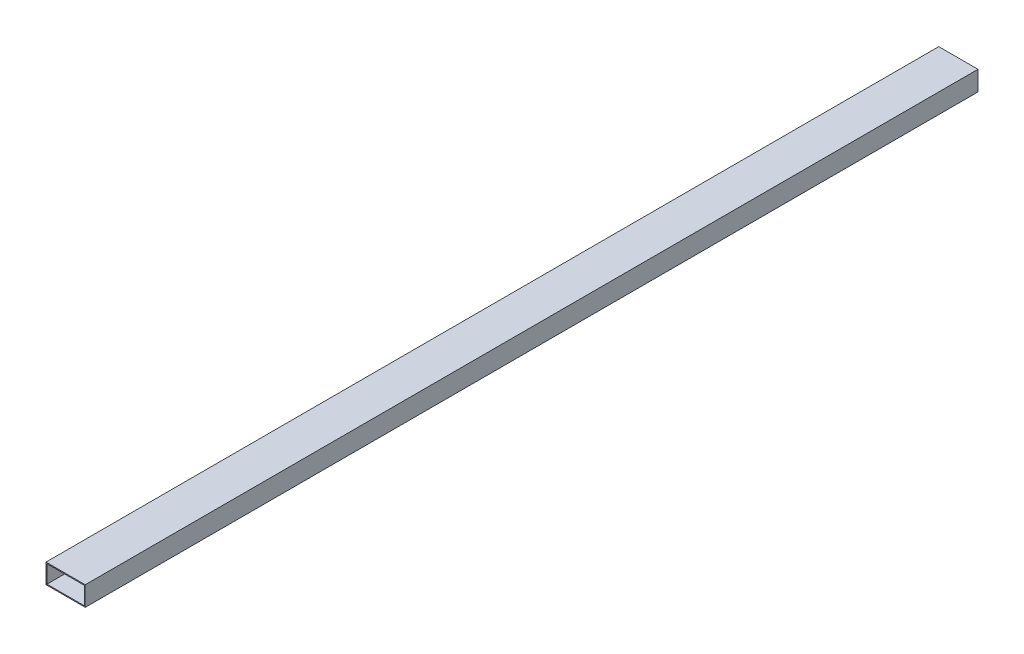
SolidWorks part; units mm, degrees
material "1060 合金"
ref_plane "前视基准面" through (0, 0, 0) normal (0, 0, 1) x (1, 0, 0)
ref_plane "上视基准面" through (0, 0, 0) normal (0, 1, 0) x (1, 0, 0)
ref_plane "右视基准面" through (0, 0, 0) normal (1, 0, 0) x (0, 0, -1)
other "Configuration Table"
sketch "草图1" plane through (0, 0, 0) normal (0, 0, 1) x (1, 0, 0)
  line L1 (-40, 20) -> (0, 20)
  line L2 (-40, 20) -> (-40, 0)
  line L3 (-40, 0) -> (0, 0)
  line L4 (0, 20) -> (0, 0)
  dimension "D1" = 20
  dimension "D2" = 40
extrude "拉伸-薄壁1" add sketch "草图1" along normal blind 910 thin thin type one direction reverse wall 1
sketch "草图2" plane through (-40, 0, 0) normal (-1, 0, 0) x (0, 0, 1)
  circle A0 centre (865, 10) radius 1.6 construction
  circle A1 centre (845, 10) radius 1.6 construction
  circle A2 centre (825, 10) radius 1.6 construction
  circle A3 centre (45, 10) radius 1.6 construction
  circle A4 centre (25, 10) radius 1.6 construction
  circle A5 centre (5, 10) radius 1.6 construction
  circle A6 centre (865, 10) radius 1.6
  circle A7 centre (845, 10) radius 1.6
  circle A8 centre (825, 10) radius 1.6
  circle A9 centre (45, 10) radius 1.6
  circle A10 centre (25, 10) radius 1.6
  circle A11 centre (5, 10) radius 1.6
extrude "切除-拉伸1" cut sketch "草图2" against normal up to next
